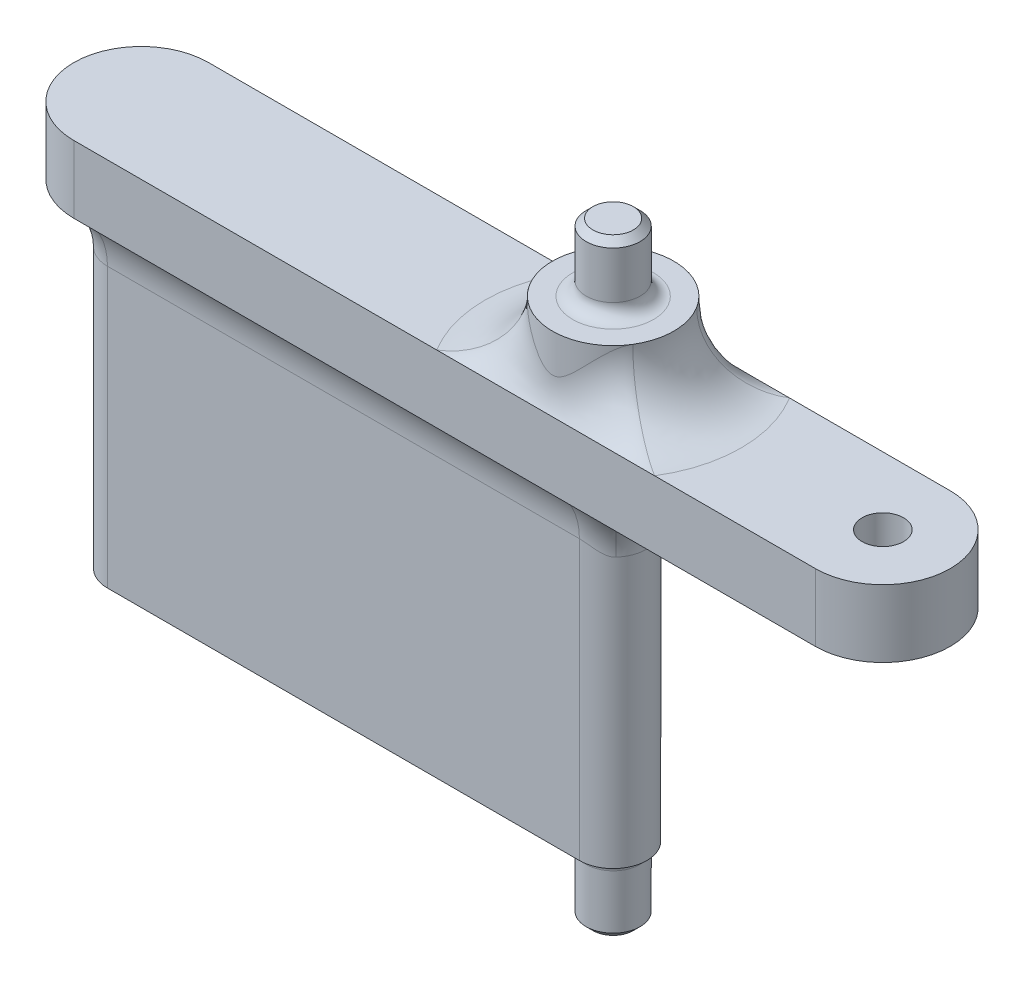
SolidWorks part; units mm, degrees
material "PET"
ref_plane "Front Plane" through (0, 0, 0) normal (0, 0, 1) x (1, 0, 0)
ref_plane "Top Plane" through (0, 0, 0) normal (0, 1, 0) x (1, 0, 0)
ref_plane "Right Plane" through (0, 0, 0) normal (1, 0, 0) x (0, 0, -1)
sketch "Sketch1" plane through (0, 0, 0) normal (0, 1, 0) x (1, 0, 0)
  line L0 (0, 0) -> (-70, 0) construction
  line L1 (0, -5) -> (-70, -5)
  line L2 (0, 5) -> (-70, 5)
  arc A0 (0, -5) -> (0, 5) centre (0, 0) ccw
  arc A1 (-70, 5) -> (-70, -5) centre (-70, 0) ccw
  point P3 (-35, 0)
  dimension "D1" = 70
  dimension "D2" = 10
extrude "Boss-Extrude1" add sketch "Sketch1" against normal blind 50
sketch "Sketch2" plane through (0, 0, 0) normal (0, 1, 0) x (1, 0, 0)
  line L0 (0, 0) -> (-70, 0) construction
  line L5 (0, -10) -> (-70, -10)
  line L6 (0, 10) -> (-70, 10)
  line L7 (0, 0) -> (40, 0) construction
  line L8 (0, 10) -> (40, 10)
  line L9 (0, -10) -> (40, -10)
  arc A5 (-70, 10) -> (-70, -10) centre (-70, 0) ccw
  arc A7 (40, -10) -> (40, 10) centre (40, 0) ccw
  circle A8 centre (40, 0) radius 3.075
  dimension "D5" = 6.15
  dimension "D7" = 10
  dimension "D1" = 70
  dimension "D2" = 20
  dimension "D3" = 20
  dimension "D4" = 40
  dimension "D6" = 70
extrude "Boss-Extrude2" add sketch "Sketch2" along normal blind 10
fillet "Fillet1" radius 10 1 edges at (5, 0, 0)
sketch "Sketch3" plane through (0, 10, 0) normal (0, 1, 0) x (1, 0, 0)
  circle A0 centre (0, 0) radius 9
  dimension "D1" = 18
extrude "Boss-Extrude3" add sketch "Sketch3" along normal blind 10
fillet "Fillet2" radius 10 1 edges at (0, 10, 9)
sketch "Sketch7" plane through (0, -50, 0) normal (0, -1, 0) x (1, 0, 0)
  circle A0 centre (0, 0) radius 4
  dimension "D1" = 8
extrude "Boss-Extrude4" add sketch "Sketch7" along normal blind 10
chamfer "Chamfer1" distance 1 angle 45 1 edges at (0, -60, -4)
sketch "Sketch8" plane through (0, 20, 0) normal (0, 1, 0) x (1, 0, 0)
  circle A1 centre (0, 0) radius 4
  dimension "D1" = 8
extrude "Boss-Extrude5" add sketch "Sketch8" along normal blind 10
chamfer "Chamfer2" distance 1 angle 45 1 edges at (0, 30, 4)
fillet "Fillet4" radius 1 1 edges at (0, -50, 4)
fillet "Fillet5" radius 2 1 edges at (0, 20, 4)
